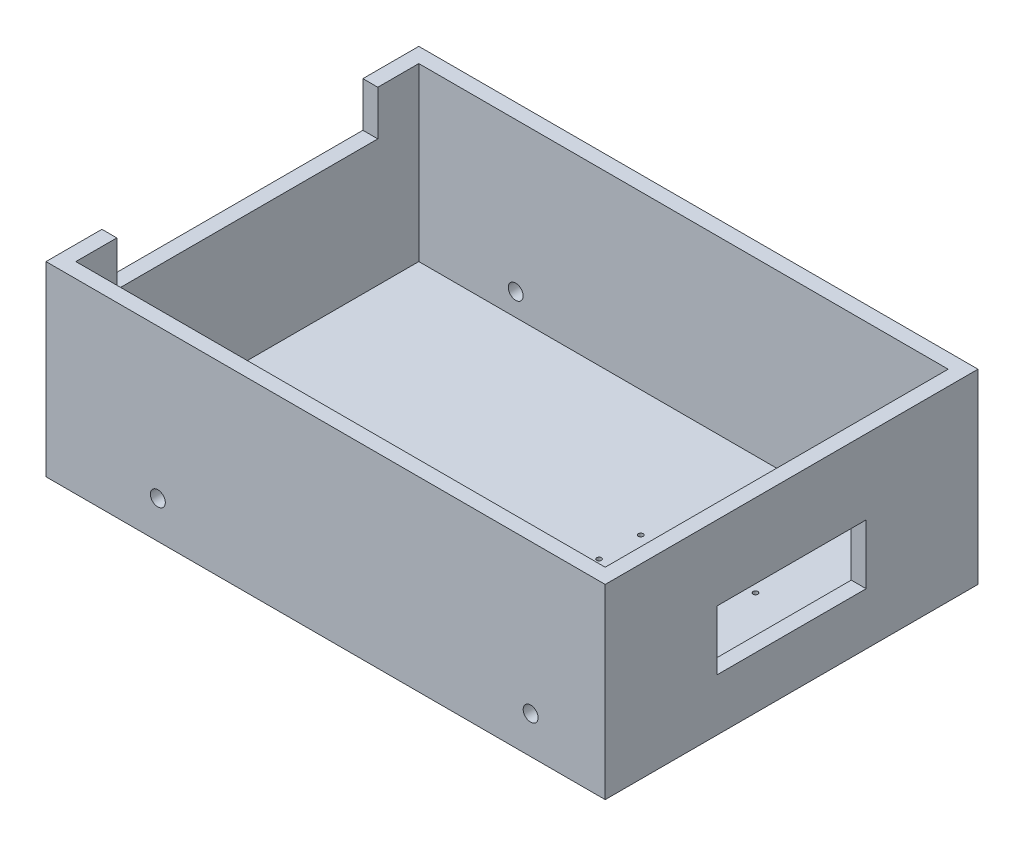
SolidWorks part; units mm, degrees
ref_plane "Front Plane" through (0, 0, 0) normal (0, 0, 1) x (1, 0, 0)
ref_plane "Top Plane" through (0, 0, 0) normal (0, 1, 0) x (1, 0, 0)
ref_plane "Right Plane" through (0, 0, 0) normal (1, 0, 0) x (0, 0, -1)
sketch "Sketch2" plane through (0, 0, 0) normal (0, 1, 0) x (1, 0, 0)
  line L1 (187.5, -125) -> (-187.5, -125)
  line L2 (187.5, -125) -> (187.5, 125)
  line L3 (187.5, 125) -> (-187.5, 125)
  line L4 (-187.5, -125) -> (-187.5, 125)
  line L5 (187.5, -125) -> (-187.5, 125) construction
  line L6 (187.5, 125) -> (-187.5, -125) construction
  point P0 (0, 0)
  dimension "D1" = 250
  dimension "D2" = 375
extrude "Boss-Extrude1" add sketch "Sketch2" along normal blind 125
shell "Shell1" thickness 10 removed face at (0, 125, 0)
sketch "Sketch3" plane through (0, 0, 0) normal (0, 0, 1) x (1, 0, 0)
  line L0 (187.5, 125) -> (187.5, 0) construction
  line L1 (-187.5, 125) -> (-187.5, 0) construction
  line L2 (-187.5, 0) -> (187.5, 0) construction
  circle A0 centre (137.5, 25) radius 5
  circle A1 centre (-112.5, 25) radius 5
  dimension "D1" = 50
  dimension "D2" = 250
  dimension "D3" = 75
  dimension "D4" = 25
  dimension "D5" = 10
extrude "Cut-Extrude1" cut sketch "Sketch3" against normal through all both and the other way through all
sketch "Sketch4" plane through (-187.5, 0, 0) normal (-1, 0, 0) x (0, 0, 1)
  line L0 (-125, 125) -> (125, 125) construction
  line L1 (-87.5, 125) -> (87.5, 125)
  line L2 (-87.5, 125) -> (-87.5, 95)
  line L3 (-87.5, 95) -> (87.5, 95)
  line L4 (87.5, 125) -> (87.5, 95)
  line L5 (-87.5, 125) -> (87.5, 95) construction
  line L6 (-87.5, 95) -> (87.5, 125) construction
  point P4 (0, 110)
  dimension "D1" = 175
  dimension "D2" = 30
extrude "Cut-Extrude2" cut sketch "Sketch4" against normal up to next and the other way through all
hole_wizard "M2 Clearance Hole1" positions "Sketch5" profile "Sketch6" hole size "M2" standard "ANSI Metric" end condition through all
sketch "Sketch5" plane through (0, 0, 0) normal (0, -1, 0) x (-1, 0, 0)
  point P0 (-100.7, -111.287)
  point P3 (-110.7, -111.287)
  point P6 (-100.7, 103.9)
  point P9 (-110.7, 103.9)
sketch "Sketch6" plane through (100.7, 0, 111.287) normal (1, 0, 0) x (0, 0, -1)
  line L0 (0, 0) -> (0, 125)
  line L1 (0, 125) -> (1.2, 125)
  line L2 (1.2, 125) -> (1.2, 0)
  line L5 (1.2, 0) -> (0, 0)
  line L11 (0, -6.35) -> (0, 107.95) construction
  dimension "Thru Hole Dia." = 2.4
  dimension "Thru Hole Depth" = 125
sketch "Sketch7" plane through (0, 10, 0) normal (0, 1, 0) x (1, 0, 0)
  line L0 (121.7567, 38.2429) -> (55.5156, 38.2429) construction
  line L1 (55.5156, 38.2429) -> (53.1767, 35.8578) construction
  line L2 (53.1767, 35.8578) -> (53.1767, -3.1481) construction
  line L3 (53.1767, -3.1481) -> (55.7167, -4.2545) construction
  line L4 (55.7167, -4.2545) -> (55.7167, -15.0971) construction
  line L5 (55.7167, -15.0971) -> (121.7567, -15.0971) construction
  line L6 (121.7567, -15.0971) -> (121.7567, 38.2429) construction
  line L7 (107.7867, 35.7029) -> (107.7867, -12.5571) construction
  point P0 (127.7856, 35.4929)
  point P2 (127.7856, -12.5571)
  point P5 (55.7167, 30.6229)
  point P8 (55.7167, 2.6829)
  point P25 (106.5167, -12.5571)
  point P27 (107.7867, 35.7029)
  point P39 (107.7867, 11.5729)
  point P40 (121.7567, 11.5729)
  point P56 (55.7167, 2.6829)
  dimension "D1" = 48.05
  dimension "D2" = 27.94
  dimension "D3" = 50.8
  dimension "D4" = 53.34
  dimension "D5" = 45.72
  dimension "D6" = 20
  dimension "D7" = 15.24
  dimension "D8" = 13.97
  dimension "D9" = 50.8
  dimension "D10" = 68.58
  dimension "D11" = 17.78
  dimension "D12" = 66.04
hole_wizard "Ø3.2 (3.2) Diameter Hole1" positions "Sketch7" profile "Sketch8" hole size "Ø3.2" standard "ANSI Metric" end condition up to next
sketch "Sketch8" plane through (127.7856, 10, -35.4929) normal (1, 0, 0) x (0, 0, 1)
  line L0 (0, 0) -> (0, 10)
  line L1 (0, 10) -> (1.6, 10)
  line L2 (1.6, 10) -> (1.6, 0)
  line L5 (1.6, 0) -> (0, 0)
  line L11 (0, -6.35) -> (0, 107.95) construction
  dimension "Thru Hole Dia." = 3.2
  dimension "Thru Hole Depth" = 10
sketch "Sketch9" plane through (187.5, 0, 0) normal (1, 0, 0) x (0, 0, -1)
  line L0 (-125, 0) -> (125, 0) construction
  line L1 (-50, 75) -> (50, 75)
  line L2 (-50, 75) -> (-50, 35)
  line L3 (-50, 35) -> (50, 35)
  line L4 (50, 75) -> (50, 35)
  line L5 (-125, 125) -> (125, 125) construction
  point P4 (0, 0)
  point P7 (0, 35)
  dimension "D1" = 100
  dimension "D2" = 40
  dimension "D3" = 50
extrude "Cut-Extrude3" cut sketch "Sketch9" against normal up to next
